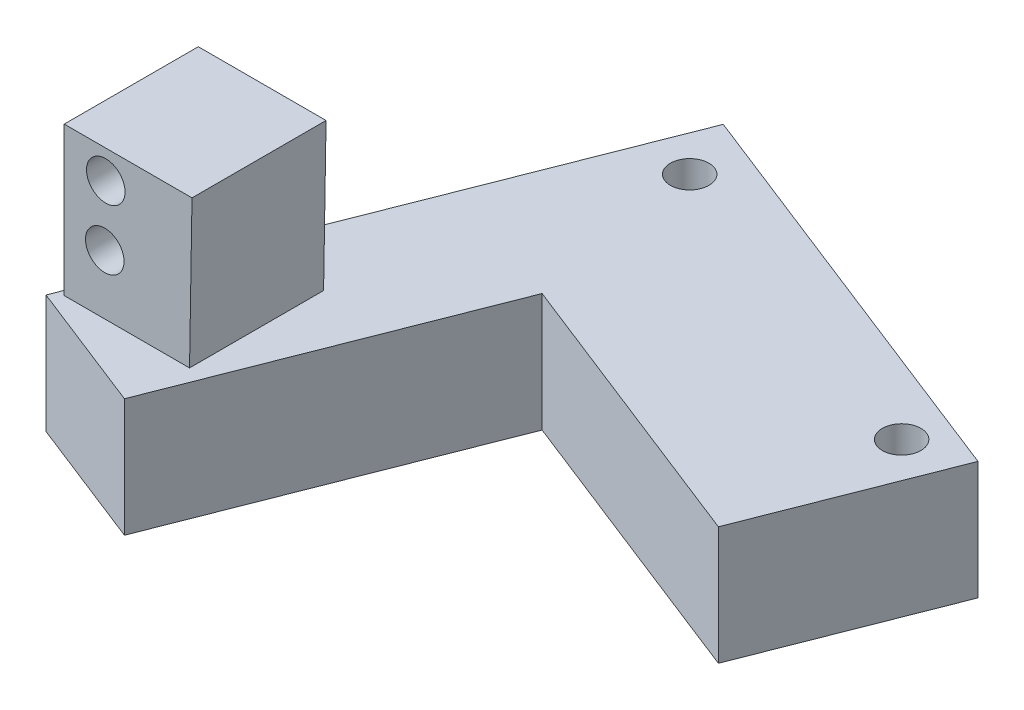
SolidWorks part; units mm, degrees
ref_plane "Front Plane" through (0, 0, 0) normal (0, 0, 1) x (1, 0, 0)
ref_plane "Top Plane" through (0, 0, 0) normal (0, 1, 0) x (1, 0, 0)
ref_plane "Right Plane" through (0, 0, 0) normal (1, 0, 0) x (0, 0, -1)
sketch "Sketch1" plane through (0, 0, 0) normal (0, 0, 1) x (1, 0, 0)
  line L0 (430.4818, 135.1883) -> (451.5463, 135.1883)
  line L1 (426.8731, 135.2483) -> (443.5981, 134.9701) construction
  line L2 (451.5463, 135.1883) -> (451.1391, 110.7021)
  line L3 (451.1391, 110.7021) -> (430.4818, 110.7021)
  line L4 (430.4818, 110.7021) -> (430.4818, 135.1883)
  line L5 (427.9702, 112.9511) -> (437.0368, 112.8004) construction
  line L6 (427.9702, 112.9511) -> (437.0368, 112.8004)
  line L7 (427.9702, 112.9511) -> (437.0368, 112.8004)
  line L8 (427.9702, 112.9511) -> (437.0368, 112.8004)
  line L9 (427.9702, 112.9511) -> (437.0368, 112.8004)
  line L10 (427.9702, 112.9511) -> (437.0368, 112.8004)
  arc A0 (444.3649, 127.3721) -> (443.5981, 134.9701) centre (437.3311, 130.5) ccw construction
  arc A1 (444.3649, 127.3721) -> (444.2998, 123.3969) centre (449.0067, 125.308) ccw construction
  arc A2 (443.2811, 115.8212) -> (444.2998, 123.3969) centre (437.1648, 120.5) ccw construction
  arc A3 (441.8282, 114.3719) -> (443.2811, 115.8212) centre (437.1648, 120.5) ccw construction
  arc A4 (437.0368, 112.8004) -> (441.8282, 114.3719) centre (437.1648, 120.5) ccw construction
  arc A5 (444.3649, 127.3721) -> (443.5981, 134.9701) centre (437.3311, 130.5) ccw
  arc A6 (444.3649, 127.3721) -> (444.2998, 123.3969) centre (449.0067, 125.308) ccw
  arc A7 (443.2811, 115.8212) -> (444.2998, 123.3969) centre (437.1648, 120.5) ccw
  arc A8 (441.8282, 114.3719) -> (443.2811, 115.8212) centre (437.1648, 120.5) ccw
  arc A9 (437.0368, 112.8004) -> (441.8282, 114.3719) centre (437.1648, 120.5) ccw
  circle A10 centre (437.3311, 130.5) radius 3.175
  circle A11 centre (437.1648, 120.5) radius 3.175
extrude "Boss-Extrude1" add sketch "Sketch1" along normal up to surface (22.098 mm away) contours L4 L3 L2 L0 A11 A10 region at (441.4313, 122.629, 0)
ref_plane "Plane1" through (0, 110.7021, 0) normal (0, 1, 0) x (1, 0, 0)
sketch "Sketch2" plane through (0, 110.7021, 0) normal (0, 1, 0) x (1, 0, 0)
  line L0 (460.3555, 56.6743) -> (529.4699, 29.5522)
  line L1 (529.4699, 29.5522) -> (517.4077, -1.1857)
  line L2 (517.4077, -1.1857) -> (469.5733, 17.5855)
  line L3 (469.5733, 17.5855) -> (450.1691, -31.8617)
  line L5 (428.889, -23.5109) -> (460.3555, 56.6743)
  line L7 (450.1691, -31.8617) -> (428.889, -23.5109)
  circle A0 centre (520.0432, 26.3896) radius 3.175
  circle A1 centre (464.7158, 46.7775) radius 3.175
  circle A2 centre (464.7158, 46.7775) radius 3.175 construction
  circle A3 centre (520.0432, 26.3896) radius 3.175 construction
  dimension "D5" = 7.62
  dimension "D9" = 6.35
  dimension "D10" = 6.35
  dimension "D2" = 22.86
  dimension "D3" = 33.02
  dimension "D4" = 7.62
  dimension "D6" = 74.2456
extrude "Boss-Extrude2" add sketch "Sketch2" against normal up to surface (19.4907 mm away)
